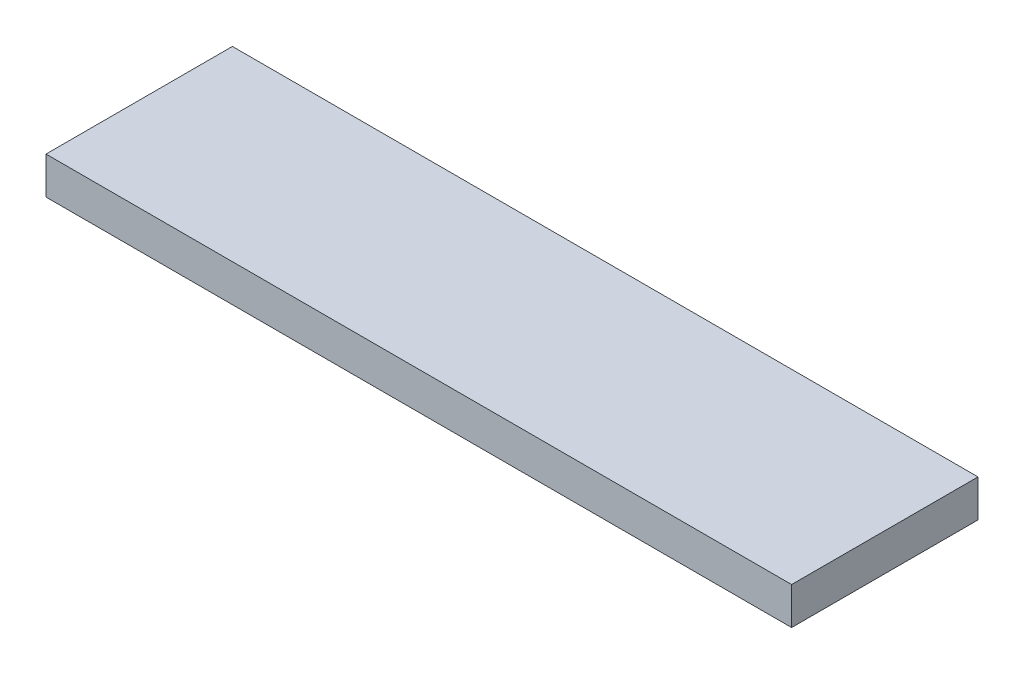
SolidWorks part; units mm, degrees
ref_plane "Front Plane" through (0, 0, 0) normal (0, 0, 1) x (1, 0, 0)
ref_plane "Top Plane" through (0, 0, 0) normal (0, 1, 0) x (1, 0, 0)
ref_plane "Right Plane" through (0, 0, 0) normal (1, 0, 0) x (0, 0, -1)
sketch "Sketch1" plane through (0, 0, 0) normal (0, 0, 1) x (1, 0, 0)
  line L1 (0, 0) -> (60, 0)
  line L2 (0, 0) -> (0, 3)
  line L3 (0, 3) -> (60, 3)
  line L4 (60, 0) -> (60, 3)
  dimension "D1" = 3
  dimension "D2" = 60
extrude "Boss-Extrude1" add sketch "Sketch1" along normal blind 15
